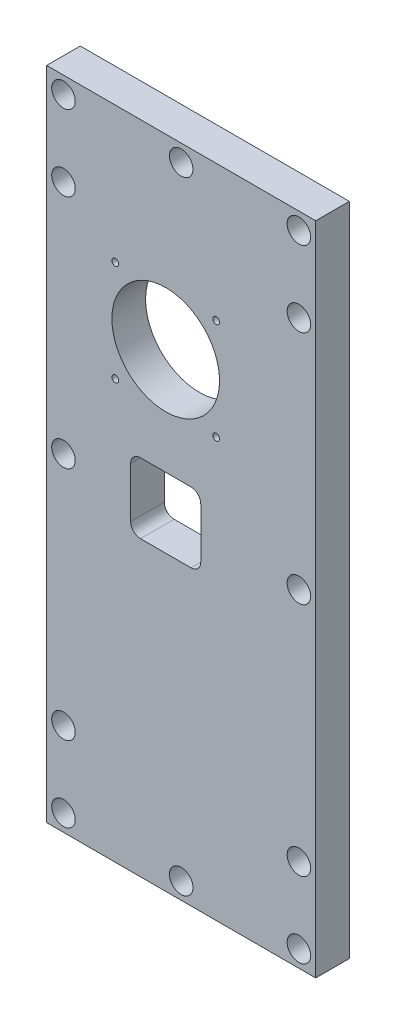
SolidWorks part; units mm, degrees
material "AISI 1020"
ref_plane "Ebene vorne" through (0, 0, 0) normal (0, 0, 1) x (1, 0, 0)
ref_plane "Ebene oben" through (0, 0, 0) normal (0, 1, 0) x (1, 0, 0)
ref_plane "Ebene rechts" through (0, 0, 0) normal (1, 0, 0) x (0, 0, -1)
sketch "Skizze1" plane through (0, 0, 0) normal (0, 0, 1) x (1, 0, 0)
  line L1 (-69.0594, 70.0995) -> (10.9406, 70.0995)
  line L2 (-69.0594, 70.0995) -> (-69.0594, -124.9005)
  line L3 (-69.0594, -124.9005) -> (10.9406, -124.9005)
  line L4 (10.9406, 70.0995) -> (10.9406, -124.9005)
  dimension "D1" = 195
  dimension "D2" = 80
extrude "Aufsatz-Linear austragen1" add sketch "Skizze1" against normal blind 10
sketch "Skizze2" plane through (0, 0, -10) normal (0, 0, -1) x (-1, 0, 0)
  line L0 (69.0594, 70.0995) -> (69.0594, -124.9005) construction
  line L1 (33.6594, 14.5995) -> (33.6594, -27.4005) construction
  line L3 (33.6594, 14.5995) -> (69.0594, 14.5995) construction
  line L5 (18.6594, 29.5995) -> (48.6594, 29.5995) construction
  line L6 (48.6594, 29.5995) -> (48.6594, -0.4005) construction
  line L7 (48.6594, -0.4005) -> (18.6594, -0.4005) construction
  line L8 (18.6594, -0.4005) -> (18.6594, 29.5995) construction
  line L9 (18.6594, 29.5995) -> (48.6594, -0.4005) construction
  line L10 (69.0594, -27.4005) -> (-10.9406, -27.4005) construction
  line L11 (-10.9406, -124.9005) -> (-10.9406, 70.0995) construction
  line L12 (23.2413, -19.9005) -> (23.2413, -34.9005)
  line L13 (26.1594, -16.9824) -> (41.1594, -16.9824)
  line L14 (44.0774, -19.9005) -> (44.0774, -34.9005)
  line L15 (41.1594, -37.8185) -> (26.1594, -37.8185)
  line L16 (23.2413, -19.9005) -> (44.0774, -34.9005) construction
  line L17 (26.1594, -37.8185) -> (41.1594, -16.9824) construction
  circle A0 centre (18.6594, 29.5995) radius 1
  circle A1 centre (48.6594, 29.5995) radius 1
  circle A2 centre (18.6594, -0.4005) radius 1
  circle A3 centre (48.6594, -0.4005) radius 1
  circle A4 centre (33.6594, 14.5995) radius 16
  arc A5 (23.2413, -19.9005) -> (26.1594, -16.9824) centre (26.1594, -19.9005) cw
  arc A6 (41.1594, -16.9824) -> (44.0774, -19.9005) centre (41.1594, -19.9005) cw
  arc A7 (44.0774, -34.9005) -> (41.1594, -37.8185) centre (41.1594, -34.9005) cw
  arc A8 (26.1594, -37.8185) -> (23.2413, -34.9005) centre (26.1594, -34.9005) cw
  point P22 (33.6594, 14.5995)
  point P32 (33.6594, -27.4005)
  dimension "D1" = 30
  dimension "D3" = 2
  dimension "D2" = 30
  dimension "D4" = 35.4
  dimension "D5" = 42
  dimension "D6" = 15
extrude "Schnitt-Linear austragen1" cut sketch "Skizze2" against normal blind 10
sketch "Skizze3" plane through (0, 0, -10) normal (0, 0, -1) x (-1, 0, 0)
  line L0 (-5.9406, 65.0995) -> (64.0594, 65.0995) construction
  line L1 (64.0594, 65.0995) -> (64.0594, 42.5995) construction
  line L2 (64.0594, 42.5995) -> (64.0594, -27.4005) construction
  line L3 (69.0594, 70.0995) -> (69.0594, -124.9005) construction
  line L4 (64.0594, -27.4005) -> (64.0594, -97.4005) construction
  line L5 (64.0594, -97.4005) -> (64.0594, -119.9005) construction
  line L6 (64.0594, -119.9005) -> (-5.9406, -119.9005) construction
  line L7 (-5.9406, -119.9005) -> (-5.9406, -97.4005) construction
  line L8 (-5.9406, -97.4005) -> (-5.9406, -27.4005) construction
  line L10 (-5.9406, -27.4005) -> (-5.9406, 42.5995) construction
  line L11 (-5.9406, 42.5995) -> (-5.9406, 65.0995) construction
  line L12 (29.0594, 65.0995) -> (29.0594, 70.0995) construction
  line L13 (-10.9406, 70.0995) -> (69.0594, 70.0995) construction
  line L14 (29.0594, -119.9005) -> (29.0594, -124.9005) construction
  line L15 (69.0594, -124.9005) -> (-10.9406, -124.9005) construction
  line L16 (-10.9406, -124.9005) -> (-10.9406, 70.0995) construction
  circle A0 centre (-5.9406, 65.0995) radius 1.7
  circle A1 centre (64.0594, 65.0995) radius 1.7
  circle A2 centre (29.0594, 65.0995) radius 1.7
  circle A3 centre (64.0594, 42.5995) radius 1.7
  circle A5 centre (64.0594, -27.4005) radius 1.7
  circle A6 centre (64.0594, -97.4005) radius 1.7
  circle A7 centre (64.0594, -119.9005) radius 1.7
  circle A8 centre (29.0594, -119.9005) radius 1.7
  circle A9 centre (-5.9406, -119.9005) radius 1.7
  circle A10 centre (-5.9406, -97.4005) radius 1.7
  circle A11 centre (-5.9406, -27.4005) radius 1.7
  circle A13 centre (-5.9406, 42.5995) radius 1.7
  dimension "D4" = 3.4
  dimension "D1" = 5
  dimension "D2" = 5
  dimension "D3" = 5
  dimension "D5" = 70
  dimension "D6" = 5
extrude "Schnitt-Linear austragen2" cut sketch "Skizze3" against normal blind 5
sketch "Skizze4" plane through (0, 0, 0) normal (0, 0, 1) x (1, 0, 0)
  line L0 (-64.0594, 65.0995) -> (-64.0594, 42.5995) construction
  line L1 (-64.0594, 42.5995) -> (-64.0594, -27.4005) construction
  line L2 (-64.0594, -27.4005) -> (-64.0594, -97.4005) construction
  line L3 (-64.0594, -97.4005) -> (-64.0594, -119.9005) construction
  line L4 (5.9406, 65.0995) -> (5.9406, 42.5995) construction
  line L5 (5.9406, -119.9005) -> (-64.0594, -119.9005) construction
  line L6 (5.9406, 42.5995) -> (5.9406, -27.4005) construction
  line L7 (5.9406, -27.4005) -> (5.9406, -97.4005) construction
  line L8 (5.9406, -97.4005) -> (5.9406, -119.9005) construction
  line L9 (-69.0594, 70.0995) -> (-69.0594, -124.9005) construction
  line L11 (-64.0594, 65.0995) -> (5.9406, 65.0995) construction
  line L12 (-29.0594, 65.0995) -> (-29.0594, 70.0995) construction
  line L13 (10.9406, 70.0995) -> (-69.0594, 70.0995) construction
  line L15 (-69.0594, -124.9005) -> (10.9406, -124.9005) construction
  circle A0 centre (-64.0594, 65.0995) radius 3.5
  circle A1 centre (5.9406, 65.0995) radius 3.5
  circle A2 centre (5.9406, 42.5995) radius 3.5
  circle A3 centre (5.9406, -27.4005) radius 3.5
  circle A5 centre (5.9406, -97.4005) radius 3.5
  circle A6 centre (5.9406, -119.9005) radius 3.5
  circle A7 centre (-64.0594, -119.9005) radius 3.5
  circle A8 centre (-64.0594, -97.4005) radius 3.5
  circle A10 centre (-64.0594, -27.4005) radius 3.5
  circle A11 centre (-64.0594, 42.5995) radius 3.5
  circle A12 centre (-29.0594, -119.9005) radius 3.5
  circle A13 centre (-29.0594, 65.0995) radius 3.5
  dimension "D4" = 7
  dimension "D1" = 70
  dimension "D2" = 5
  dimension "D3" = 5
  dimension "D5" = 5
extrude "Schnitt-Linear austragen3" cut sketch "Skizze4" against normal blind 5
sketch "Skizze5" plane through (-69.0594, 0, 0) normal (-1, 0, 0) x (0, 0, 1)
  line L0 (0, 14.5995) -> (-10, 14.5995) construction
  line L1 (-5, 14.5995) -> (-5, -0.4005) construction
  line L2 (-5, 14.5995) -> (-5, 29.5995) construction
  line L3 (-10, 70.0995) -> (-10, -124.9005) construction
  line L4 (0, 70.0995) -> (0, -124.9005) construction
  line L5 (-10, 70.0995) -> (0, 70.0995) construction
  circle A0 centre (-5, 29.5995) radius 1
  circle A1 centre (-5, -0.4005) radius 1
  dimension "D1" = 2
  dimension "D2" = 30
  dimension "D3" = 55.5
sketch "Skizze6" plane through (10.9406, 0, 0) normal (1, 0, 0) x (0, 0, -1)
  line L0 (10, 14.5995) -> (0, 14.5995) construction
  line L1 (5, 14.5995) -> (5, -0.4005) construction
  line L2 (5, 14.5995) -> (5, 29.5995) construction
  line L3 (0, -124.9005) -> (0, 70.0995) construction
  line L4 (10, -124.9005) -> (10, 70.0995) construction
  line L5 (10, 70.0995) -> (0, 70.0995) construction
  circle A0 centre (5, 29.5995) radius 1
  circle A1 centre (5, -0.4005) radius 1
  dimension "D1" = 2
  dimension "D2" = 30
  dimension "D3" = 55.5
